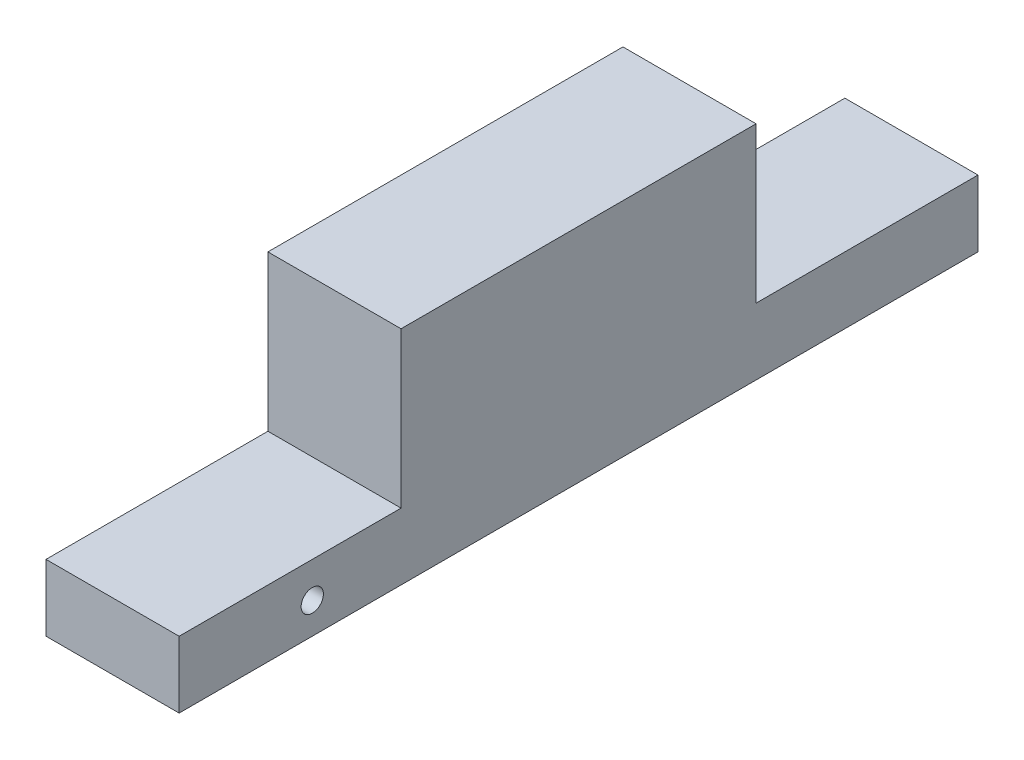
SolidWorks part; units mm, degrees
ref_plane "xy_plane" through (0, 0, 0) normal (0, 0, 1) x (1, 0, 0)
ref_plane "zx_plane" through (0, 0, 0) normal (0, 1, 0) x (1, 0, 0)
ref_plane "yz_plane" through (0, 0, 0) normal (1, 0, 0) x (0, 0, -1)
ref_axis "x_axis" through (-80.9, 0, 0) along (1, 0, 0)
ref_axis "y_axis" through (0, -50, 0) along (0, 1, 0)
ref_axis "z_axis" through (0, 0, -80.9) along (0, 0, 1)
ref_plane "xMid_plane" through (0, 0, 0) normal (1, 0, 0) x (0, 0, -1)
ref_plane "xMin_plane" through (-15, 0, 0) normal (1, 0, 0) x (0, 0, -1)
ref_plane "xMax_plane" through (15, 0, 0) normal (1, 0, 0) x (0, 0, -1)
ref_plane "yMid_plane" through (0, 0, 0) normal (0, 1, 0) x (1, 0, 0)
ref_plane "yMin_plane" through (0, -25, 0) normal (0, 1, 0) x (1, 0, 0)
ref_plane "yMax_plane" through (0, 25, 0) normal (0, 1, 0) x (1, 0, 0)
ref_plane "zMid_plane"
ref_plane "zMin_plane" through (0, 0, -90) normal (0, 0, 1) x (1, 0, 0)
ref_plane "zMax_plane" through (0, 0, 90) normal (0, 0, 1) x (1, 0, 0)
sketch "projectionYz_sketch" plane through (0, 0, 0) normal (1, 0, 0) x (0, 0, -1)
  line L0 (90, -25) -> (90, -10)
  line L1 (90, -10) -> (40, -10)
  line L2 (40, -10) -> (40, 25)
  line L3 (40, 25) -> (-40, 25)
  line L4 (-40, 25) -> (-40, -10)
  line L5 (-40, -10) -> (-90, -10)
  line L6 (-90, -10) -> (-90, -25)
  line L7 (90, -25) -> (-90, -25)
  line L8 (90, 55) -> (90, -55) construction
  line L9 (55, -25) -> (-55, -25) construction
  line L10 (-90, 55) -> (-90, -55) construction
  line L11 (40, 80) -> (40, -30) construction
  line L12 (-40, 80) -> (-40, -30) construction
  line L13 (55, 25) -> (-55, 25) construction
  dimension "D1" = 15
extrude "mainBody_extrude" add sketch "projectionYz_sketch" along normal up to surface (15 mm away) from surface up to plane "xMax_plane" starting at plane "xMin_plane"
sketch "pivotShaftHole_sketch" plane through (0, 0, 0) normal (1, 0, 0) x (0, 0, -1)
  circle A0 centre (-60, -18) radius 2.51
  dimension "D1" = 5.02
extrude "pivotShaftHole_cut" cut sketch "pivotShaftHole_sketch" against normal through all both and the other way through all from surface starting at plane "xMid_plane"
equation "\"D1@xMin_plane\" = \"externalParameters.this.extent.x\" / 2"
equation "\"D1@xMax_plane\" = \"externalParameters.this.extent.x\" / 2"
equation "\"D1@yMin_plane\" = \"externalParameters.this.extent.y\" / 2"
equation "\"D1@yMax_plane\"= \"externalParameters.this.extent.y\" / 2"
equation "\"D1@zMin_plane\" = \"externalParameters.this.extent.z\" / 2"
equation "\"D1@zMax_plane\" = \"externalParameters.this.extent.z\" / 2"
equation "\"D1@projectionYz_sketch\" = \"externalParameters.this.foot.extent.y\""
equation "\"D1@pivotShaftHole_sketch\"=\"externalParameters.pivotShaft.holeDiameter\""
